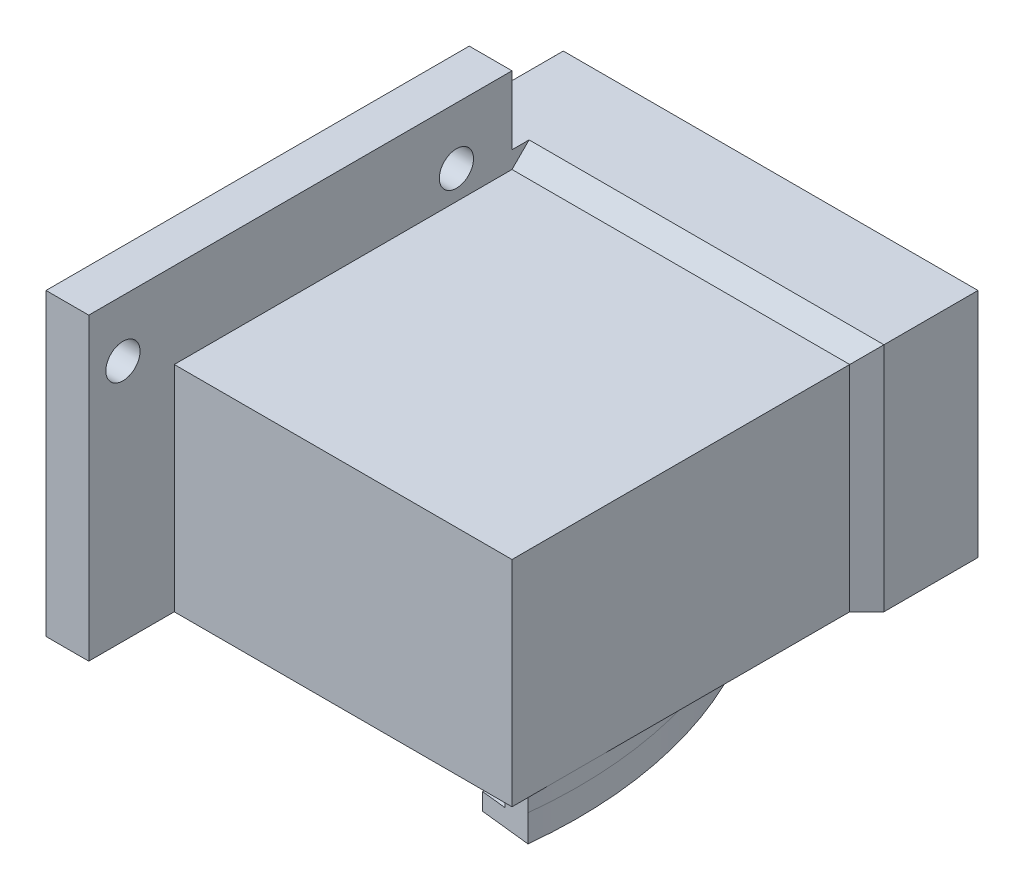
SolidWorks part; units mm, degrees
ref_plane "Płaszczyzna przednia" through (0, 0, 0) normal (0, 0, 1) x (1, 0, 0)
ref_plane "Płaszczyzna górna" through (0, 0, 0) normal (0, 1, 0) x (1, 0, 0)
ref_plane "Płaszczyzna prawa" through (0, 0, 0) normal (1, 0, 0) x (0, 0, -1)
sketch "Sketch1" plane through (0, 0, 0) normal (0, 0, 1) x (1, 0, 0)
  line L0 (-22.25, 11.525) -> (22.25, 11.525)
  line L1 (-19.95, 9.225) -> (19.95, 9.225)
  line L2 (-19.95, 9.225) -> (-19.95, -9.225)
  line L3 (-19.95, -9.225) -> (19.95, -9.225)
  line L4 (19.95, 9.225) -> (19.95, -9.225)
  line L5 (-19.95, 9.225) -> (19.95, -9.225) construction
  line L6 (-19.95, -9.225) -> (19.95, 9.225) construction
  line L7 (22.25, 11.525) -> (22.25, -11.525)
  line L8 (-22.25, -11.525) -> (22.25, -11.525)
  line L9 (-22.25, 11.525) -> (-22.25, -11.525)
  line L10 (-24.25, 13.525) -> (24.25, 13.525)
  line L11 (24.25, 13.525) -> (24.25, -13.525)
  line L12 (-24.25, -13.525) -> (24.25, -13.525)
  line L13 (-24.25, 13.525) -> (-24.25, -13.525)
  line L14 (22.25, -11.525) -> (22.25, -13.525)
  line L15 (-22.25, -11.525) -> (-22.25, -13.525)
  point P0 (0, 0)
  dimension "D1" = 39.9
  dimension "D2" = 18.45
  dimension "D5" = 23.05
  dimension "D6" = 44.5
  dimension "D3" = 2.3
  dimension "D4" = 2
extrude "Boss-Extrude1" add sketch "Sketch1" along normal blind 40 contours L8 L15 L12 L14 | L0 L7 L8 L9 | L1 L4 L3 L2 region at (0, -12.525, 0)
extrude "Boss-Extrude2" add sketch "Sketch1<3>" along normal blind 2.5 from surface contours L8 L15 L12 L14 | L0 L7 L8 L9 region at (0, -12.525, 0) starting at face at (0, -1, 40)
sketch "Sketch1<3>" plane through (0, 0, 0) normal (0, 0, 1) x (1, 0, 0) same geometry as "Sketch1"
extrude "Boss-Extrude3" add sketch "Sketch1<4>" along normal blind 3 and the other way blind 10 contours L10 L11 L12 L13 | L0 L7 L8 L9
sketch "Sketch1<4>" plane through (0, 0, 0) normal (0, 0, 1) x (1, 0, 0) same geometry as "Sketch1"
sketch "Sketch2" plane through (0, 0, 42.5) normal (0, 0, 1) x (1, 0, 0)
  line L1 (-22.25, 11.525) -> (-17.25, 11.525)
  line L2 (-22.25, 11.525) -> (-22.25, -13.525)
  line L3 (-22.25, -13.525) -> (-17.25, -13.525)
  line L4 (-17.25, 11.525) -> (-17.25, -13.525)
  line L5 (22.25, -13.525) -> (-22.25, -13.525) construction
  dimension "D1" = 5
extrude "Boss-Extrude4" add sketch "Sketch2" along normal blind 10
sketch "Sketch4" plane through (0, -13.525, 0) normal (0, -1, 0) x (1, 0, 0)
  line L0 (-14.5656, 40) -> (14.4424, 40)
  line L2 (-14.5656, 40) -> (-14.5656, 28.891)
  line L3 (-8.5656, 22.891) -> (13.124, 22.891)
  line L4 (20.2074, 34.6073) -> (20.2074, 34.5836)
  line L6 (22.25, 42.5) -> (22.25, 3) construction
  line L7 (22.25, 42.5) -> (-17.25, 42.5) construction
  arc A1 (13.124, 22.891) -> (14.4424, 40) centre (-29.1, 34.75) ccw
  arc A2 (1.0099, -3.0801) -> (18.9641, 40) centre (-29.1, 34.75) ccw
  arc A3 (21.2714, 24.7729) -> (22.1969, 37.0849) centre (-29.1, 34.75) ccw
  arc A4 (-14.5656, 28.891) -> (-8.5656, 22.891) centre (-8.5656, 28.891) ccw
  dimension "D2" = 2.5
  dimension "D1" = 3
  dimension "D3" = 6
ref_plane "Plane1" through (18.9641, -13.525, 40) normal (-0.1086, 0, 0.9941) x (0.9941, 0, 0.1086)
sketch "Sketch6" plane through (18.9641, -13.525, 40) normal (-0.1086, 0, 0.9941) x (0.9941, 0, 0.1086)
  line L0 (-999.9441, 0) -> (49000.0559, 0) construction
  line L1 (0, -1000.3743) -> (0, 48999.6257) construction
  line L2 (-0.0072, -3) -> (-3.0072, -3)
  line L3 (-0.0072, 0) -> (2.9928, 0)
  line L4 (-0.0072, 0) -> (-0.0072, -3)
  line L6 (2.9928, 0) -> (2.9928, -1.8481)
  line L8 (2.9928, -1.8481) -> (2.9928, -5)
  line L9 (2.9928, -5) -> (-3.0072, -5)
  line L10 (-3.0072, -3) -> (-3.0072, -5)
  dimension "D1" = 3
  dimension "D2" = 3
  dimension "D3" = 6
  dimension "D4" = 5
sweep "Sweep1" add profiles "Sketch6" path "Sketch4"
extrude "Cut-Extrude1" cut sketch "Sketch4<3>" against normal up to next contours L3 A1 L0 L2 region at (0.1044, -13.525, 31.6254)
sketch "Sketch4<3>" plane through (0, -13.525, 0) normal (0, -1, 0) x (1, 0, 0) same geometry as "Sketch4"
sketch "Sketch7" plane through (0, 11.525, 0) normal (0, 1, 0) x (1, 0, 0)
  line L0 (-17.25, -52.5) -> (-17.25, -42.5) construction
  line L1 (-22.25, -52.5) -> (-17.25, -52.5)
  line L2 (-22.25, -52.5) -> (-22.25, -3)
  line L3 (-22.25, -3) -> (-17.25, -3)
  line L4 (-17.25, -52.5) -> (-17.25, -3)
  line L5 (-24.25, -3) -> (24.25, -3) construction
extrude "Boss-Extrude5" add sketch "Sketch7" along normal blind 10
sketch "Sketch8" plane through (-22.25, 0, 0) normal (-1, 0, 0) x (0, 0, 1)
  circle A0 centre (48.5, 14.875) radius 2
  circle A1 centre (9.5, 14.875) radius 2
  dimension "D1" = 4
extrude "Cut-Extrude2" cut sketch "Sketch8" against normal blind 5.8
chamfer "Chamfer1" distance 2 angle 45 1 edges at (3.5, 13.525, 3)
chamfer "Chamfer2" distance 2 angle 45 1 edges at (24.25, -1, 3)
